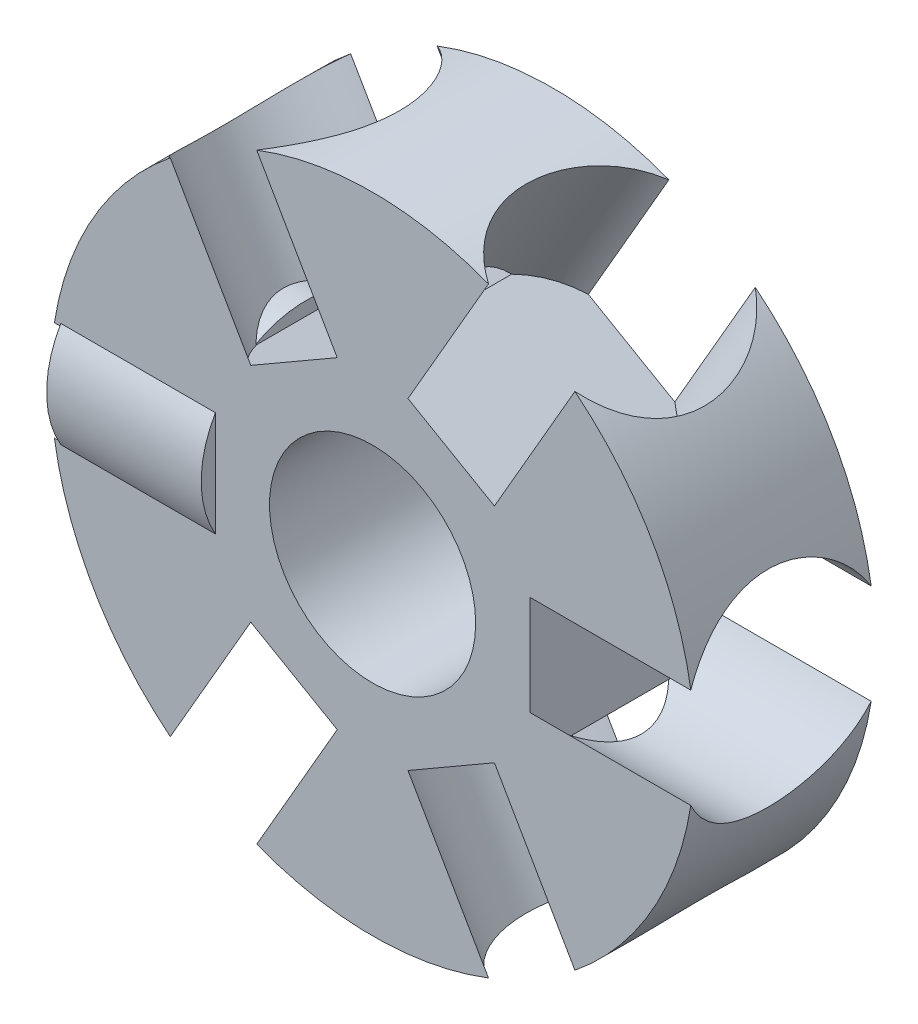
SolidWorks part; units mm, degrees
ref_plane "Top Plane" through (0, 0, 0) normal (0, 0, 1) x (1, 0, 0)
ref_plane "Right Plane" through (0, 0, 0) normal (0, 1, 0) x (1, 0, 0)
ref_plane "Front Plane" through (0, 0, 0) normal (1, 0, 0) x (0, 0, -1)
ref_axis "x-axis" through (-88.99, 0, 0) along (1, 0, 0)
ref_axis "y-axis" through (0, -55, 0) along (0, 1, 0)
ref_axis "z-axis" through (0, 0, 55) along (0, 0, -1)
sketch "Sketch1" plane through (0, 0, 0) normal (0, 0, 1) x (1, 0, 0)
  line L8 (-19.9785, 0) -> (0, 0) construction
  line L16 (0, 0) -> (0, -20.7846) construction
  line L23 (0, 0) -> (0, -20.7846) construction
  circle A0 centre (0, 0) radius 4
  circle A3 centre (0, 0) radius 12.5
  dimension "D1" = 8
  dimension "D2" = 25
extrude "Boss-Extrude1" add sketch "Sketch1" along normal mid plane 7
ref_plane "Plane1" through (-12.5, 0, 0) normal (-1, 0, 0) x (0, 0, 1)
sketch "Sketch2" plane through (-12.5, -17.1931, 0) normal (1, 0, 0) x (0, -1, 0)
  circle A0 centre (-17.1931, 0) radius 4
  dimension "D1" = 8
extrude "Cut-Extrude3" cut sketch "Sketch2" along normal blind 6.4
pattern_circular "CirPattern1" count 6 over 360 about axis through (0, 0, 3.5) along (0, 0, 1) of "Cut-Extrude3"
sketch "Sketch3" plane through (-6.1, 0, 0) normal (-1, 0, 0) x (0, -1, 0)
  circle A0 centre (0, 0) radius 4.05
  dimension "D1" = 4.05
extrude "Boss-Extrude2" add sketch "Sketch3" along normal blind 6
